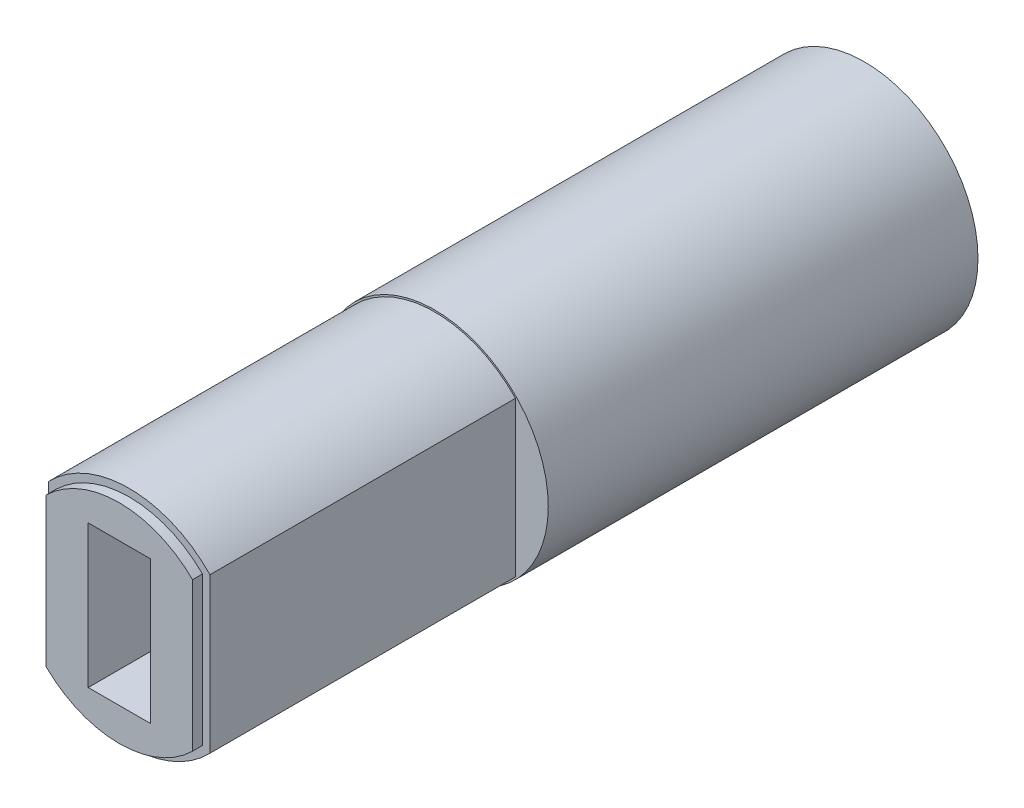
SolidWorks part; units mm, degrees
material "PF"
ref_plane "Front Plane" through (0, 0, 0) normal (0, 0, 1) x (1, 0, 0)
ref_plane "Top Plane" through (0, 0, 0) normal (0, 1, 0) x (1, 0, 0)
ref_plane "Right Plane" through (0, 0, 0) normal (1, 0, 0) x (0, 0, -1)
sketch "Sketch2" plane through (0, 0, 0) normal (0, 0, 1) x (1, 0, 0)
  circle A0 centre (0, 0) radius 4.57
  dimension "D1" = 9.14
extrude "Boss-Extrude1" add sketch "Sketch2" along normal blind 17.3
sketch "Sketch4" plane through (0, 0, 17.3) normal (0, 0, 1) x (1, 0, 0)
  line L0 (0, 0) -> (-3.25, 0) construction
  line L1 (0, 0) -> (3.25, 0) construction
  line L2 (-3.25, 3.1125) -> (-3.25, -3.1125)
  line L3 (0, 0) -> (0, 1.6894) construction
  line L4 (3.25, 3.1125) -> (3.25, -3.1125)
  arc A0 (-3.25, -3.1125) -> (3.25, -3.1125) centre (0, 0) ccw
  arc A1 (3.25, 3.1125) -> (-3.25, 3.1125) centre (0, 0) ccw
  dimension "D1" = 9
  dimension "D2" = 6.5
extrude "Boss-Extrude3" add sketch "Sketch4" along normal offset from surface (12.7 mm away) 30 up to face at (4.57, 0, 0)
sketch "Sketch5" plane through (0, 0, 30) normal (0, 0, 1) x (1, 0, 0)
  line L1 (-1.25, 2.87) -> (1.25, 2.87)
  line L2 (-1.25, 2.87) -> (-1.25, -2.87)
  line L3 (-1.25, -2.87) -> (1.25, -2.87)
  line L4 (1.25, 2.87) -> (1.25, -2.87)
  point P4 (-1.25, 0)
  point P6 (0, 2.87)
  dimension "D1" = 5.74
  dimension "D2" = 2.5
extrude "Cut-Extrude1" cut sketch "Sketch5" against normal through all
sketch "Sketch6" plane through (0, 0, 30) normal (0, 0, 1) x (1, 0, 0)
  line L0 (0, 4.2) -> (0, 4.5) construction
  line L1 (-2.95, 2.9896) -> (-2.95, -2.9896)
  line L2 (-3.25, 3.1125) -> (-3.25, -3.1125) construction
  line L3 (2.95, 2.9896) -> (2.95, -2.9896)
  line L4 (-3.25, -3.1125) -> (-3.25, 3.1125)
  line L5 (-3.25, 3.1125) -> (-3.25, -3.1125) construction
  line L6 (3.25, -3.1125) -> (3.25, 3.1125)
  arc A0 (-2.95, -2.9896) -> (2.95, -2.9896) centre (0, 0) ccw
  arc A1 (3.25, 3.1125) -> (-3.25, 3.1125) centre (0, 0) ccw construction
  arc A2 (2.95, 2.9896) -> (-2.95, 2.9896) centre (0, 0) ccw
  circle A3 centre (0, 0) radius 4.5
  line M10 (3.25, -3.1125) -> (3.25, 3.1125)
  arc M11 (3.25, 3.1125) -> (-3.25, 3.1125) centre (0, 0) ccw
  line M12 (-3.25, 3.1125) -> (-3.25, -3.1125)
  arc M13 (-3.25, -3.1125) -> (3.25, -3.1125) centre (0, 0) ccw
  dimension "D1" = 8.4
  dimension "D2" = 0.3
extrude "Cut-Extrude3" cut sketch "Sketch6" against normal blind 0.4 contours A2 L3 A0 L1 A3 M12 M13 M10 M11 region at (-3.139, 0, 30)
